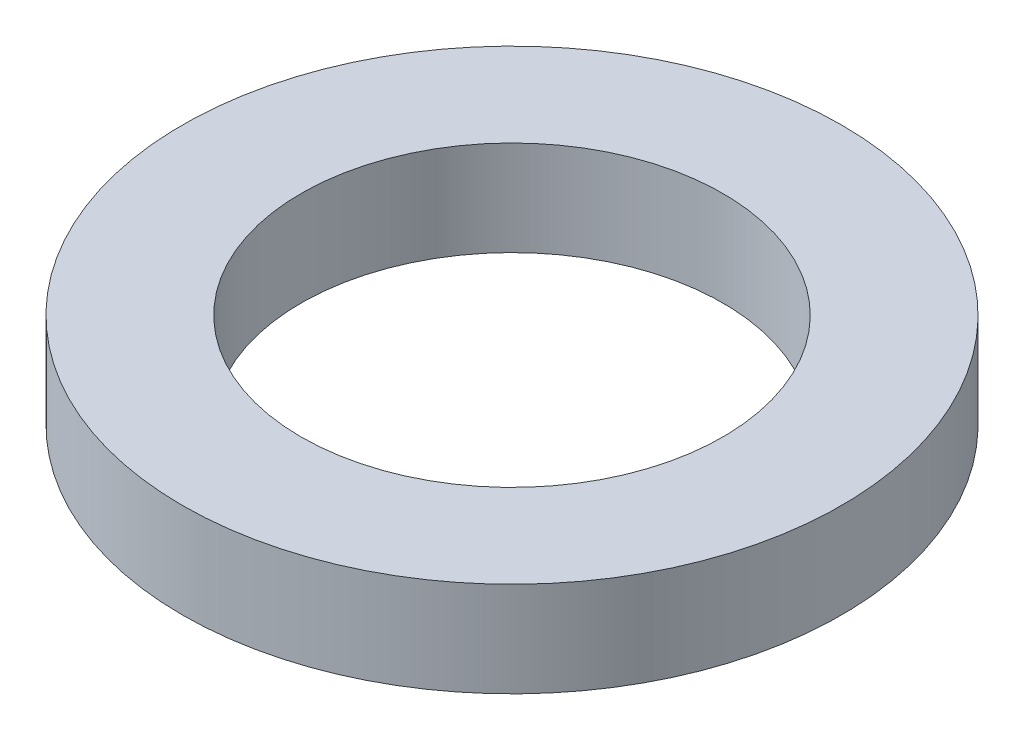
SolidWorks part; units mm, degrees
ref_plane "Front Plane" through (0, 0, 0) normal (0, 0, 1) x (1, 0, 0)
ref_plane "Top Plane" through (0, 0, 0) normal (0, 1, 0) x (1, 0, 0)
ref_plane "Right Plane" through (0, 0, 0) normal (1, 0, 0) x (0, 0, -1)
sketch "Sketch1" plane through (0, 0, 0) normal (0, 1, 0) x (1, 0, 0)
  circle A0 centre (0, 0) radius 62.5
  dimension "FLANGE_OD" = 125
extrude "Boss-Extrude1" add sketch "Sketch1" along normal blind 18
sketch "Sketch2" plane through (0, 0, 0) normal (0, 1, 0) x (1, 0, 0)
  circle A0 centre (0, 0) radius 40
  dimension "BORE_D" = 80
extrude "Cut-Extrude1" cut sketch "Sketch2" along normal through all
sketch "Sketch3" plane through (0, 18, 0) normal (0, 1, 0) x (1, 0, 0)
  circle A0 centre (0, 0) radius 23.6764 construction
  circle A1 centre (-23.6764, 0) radius 2.6877
  dimension "BOLT_D" = 5.3755
  dimension "BOLT_PCD" = 47.3528
extrude "Cut-Extrude2" cut sketch "Sketch3" against normal blind 14.3627 rebuild error yes
pattern_circular "CirPattern1" count 8 over 360 rebuild error yes
